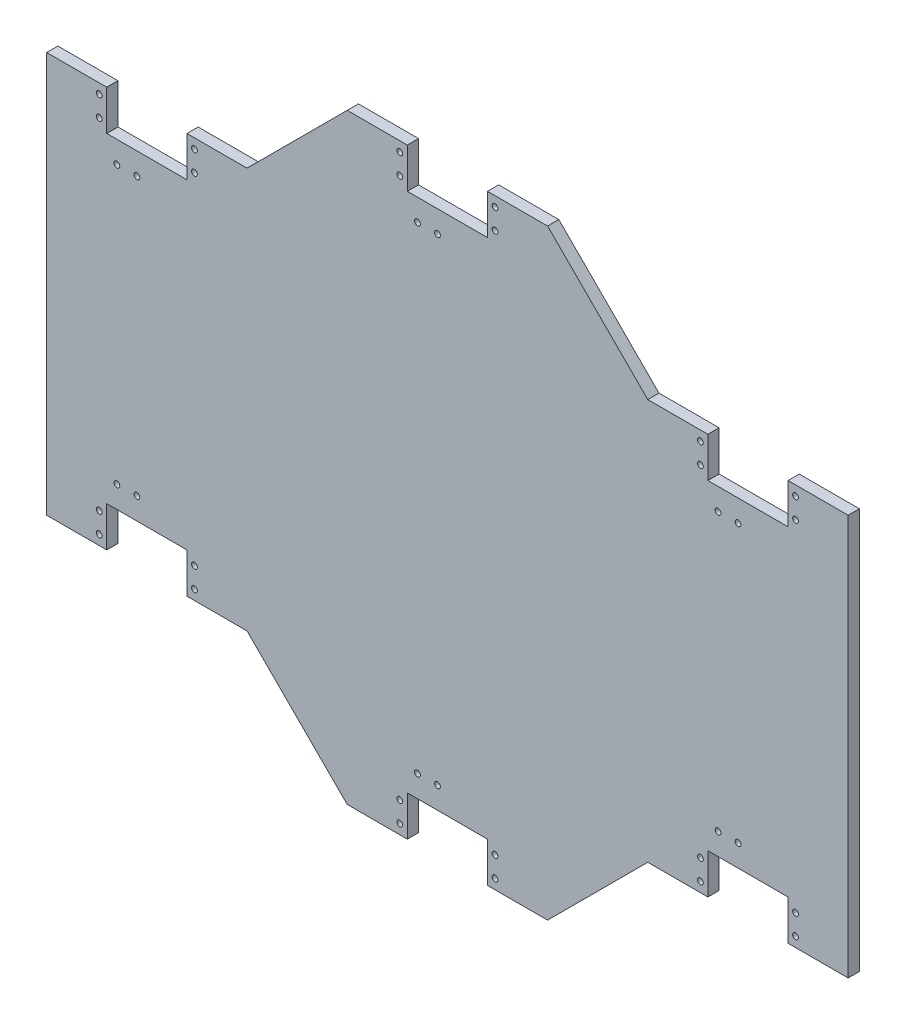
SolidWorks part; units mm, degrees
ref_plane "Front" through (0, 0, 0) normal (0, 0, 1) x (1, 0, 0)
ref_plane "Top" through (0, 0, 0) normal (0, 1, 0) x (1, 0, 0)
ref_plane "Right" through (0, 0, 0) normal (1, 0, 0) x (0, 0, -1)
sketch "Esquisse1" plane through (0, 0, 0) normal (0, 0, 1) x (1, 0, 0)
  line L0 (100, -100) -> (150, -150)
  line L1 (0, 0) -> (25.8386, 0)
  line L2 (0, 0) -> (0, -100)
  line L3 (0, -100) -> (100, -100)
  line L5 (0, 0) -> (100, -100) construction
  line L6 (0, -100) -> (25.8386, 0) construction
  line L7 (150, -150) -> (250, -150)
  line L8 (250, -150) -> (300, -100)
  line L9 (300, -100) -> (400, -100)
  line L10 (400, -100) -> (400, 0)
  line L11 (400, 0) -> (25.8386, 0)
  point P0 (0, 0)
  dimension "D1" = 100
  dimension "D2" = 100
  dimension "D3" = 100
  dimension "D4" = 135
  dimension "D5" = 135
  dimension "D6" = 0
  dimension "D7" = 50
  dimension "D8" = 100
extrude "Boss.-Extru.1" add sketch "Esquisse1" along normal blind 5.6
sketch "Esquisse2" plane through (0, 0, 5.6) normal (0, 0, 1) x (1, 0, 0)
  line L0 (0, -100) -> (100, -100) construction
  line L1 (30, -80) -> (70, -80)
  line L2 (30, -80) -> (30, -100)
  line L3 (30, -100) -> (70, -100)
  line L4 (70, -80) -> (70, -100)
  line L5 (30, -80) -> (70, -100) construction
  line L6 (30, -100) -> (70, -80) construction
  line L7 (0, 0) -> (0, -100) construction
  point P0 (0, -90)
  dimension "D1" = 20
  dimension "D2" = 40
  dimension "D3" = 30
extrude "Enlèv. mat.-Extru.1" cut sketch "Esquisse2" against normal up to next
sketch "Esquisse3" plane through (0, 0, 5.6) normal (0, 0, 1) x (1, 0, 0)
  line L0 (30, -90) -> (70, -90) construction
  line L1 (30, -80) -> (30, -100) construction
  line L2 (70, -100) -> (70, -80) construction
  circle A0 centre (26.25, -95.08) radius 1.45
  circle A1 centre (73.75, -95.08) radius 1.45
  circle A2 centre (73.75, -84.92) radius 1.45
  circle A3 centre (26.25, -84.92) radius 1.45
  circle A4 centre (35.06, -69.09) radius 1.45
  circle A5 centre (45.06, -69.09) radius 1.45
  dimension "D1" = 3.75
  dimension "D2" = 5.08
  dimension "D3" = 47.5
  dimension "D4" = 2.9
  dimension "D5" = 3.75
  dimension "D6" = 2.9
  dimension "D7" = 2.9
  dimension "D8" = 10
  dimension "D9" = 8.81
  dimension "D10" = 15.83
extrude "Enlèv. mat.-Extru.2" cut sketch "Esquisse3" against normal up to next
sketch "Sketch2" plane through (0, 0, 0) normal (0, 0, 1) x (1, 0, 0)
  line L0 (150, -150) -> (250, -150) construction
  line L1 (330, -80) -> (370, -80)
  line L2 (330, -80) -> (330, -100)
  line L3 (330, -100) -> (370, -100)
  line L4 (370, -80) -> (370, -100)
  line L5 (330, -80) -> (370, -100) construction
  line L6 (330, -100) -> (370, -80) construction
  line L7 (300, -100) -> (400, -100) construction
  line L8 (400, -100) -> (400, 0) construction
  line L9 (180, -130) -> (220, -130)
  line L10 (180, -130) -> (180, -150)
  line L11 (180, -150) -> (220, -150)
  line L12 (220, -130) -> (220, -150)
  line L13 (180, -130) -> (220, -150) construction
  line L14 (180, -150) -> (220, -130) construction
  point P0 (0, -90)
  point P11 (-35, 0)
  dimension "D1" = 20
  dimension "D2" = 40
  dimension "D3" = 30
  dimension "D4" = 40
  dimension "D5" = 20
  dimension "D6" = 30
extrude "Cut-Extrude2" cut sketch "Sketch2" against normal through all and the other way through all
sketch "Sketch5" plane through (0, 0, 0) normal (0, 0, 1) x (1, 0, 0)
  line L0 (180, -140) -> (220, -140) construction
  line L1 (220, -150) -> (220, -130) construction
  line L2 (330, -90) -> (370, -90) construction
  line L4 (370, -100) -> (370, -80) construction
  line L5 (330, -80) -> (330, -100) construction
  circle A0 centre (176.25, -145.08) radius 1.45
  circle A1 centre (223.75, -145.08) radius 1.45
  circle A2 centre (223.75, -134.92) radius 1.45
  circle A3 centre (176.25, -134.92) radius 1.45
  circle A4 centre (326.25, -95.08) radius 1.45
  circle A5 centre (373.75, -95.08) radius 1.45
  circle A6 centre (373.75, -84.92) radius 1.45
  circle A7 centre (326.25, -84.92) radius 1.45
  circle A8 centre (185.06, -119.09) radius 1.45
  circle A9 centre (195.06, -119.09) radius 1.45
  circle A10 centre (335.06, -69.09) radius 1.45
  circle A11 centre (345.06, -69.09) radius 1.45
  point P34 (0, 0)
  point P35 (0, 0)
  dimension "D1" = 5.08
  dimension "D2" = 5.08
  dimension "D3" = 47.5
  dimension "D4" = 2.9
  dimension "D5" = 3.75
  dimension "D10" = 2.9
  dimension "D11" = 2.9
  dimension "D12" = 2.9
  dimension "D16" = 2.9
  dimension "D17" = 2.9
  dimension "D6" = 5.08
  dimension "D7" = 5.08
  dimension "D8" = 3.75
  dimension "D9" = 3.75
  dimension "D13" = 10
  dimension "D14" = 8.81
  dimension "D15" = 15.83
  dimension "D18" = 8.81
  dimension "D19" = 15.83
  dimension "D20" = 10
  dimension "D21" = 0
extrude "Cut-Extrude4" cut sketch "Sketch5" along normal through all
mirror "Mirror1" about plane through (0, 0, 0) normal (0, 1, 0) of "Cut-Extrude4", "Cut-Extrude2", "Enlèv. mat.-Extru.1", "Enlèv. mat.-Extru.2", "Boss.-Extru.1"
